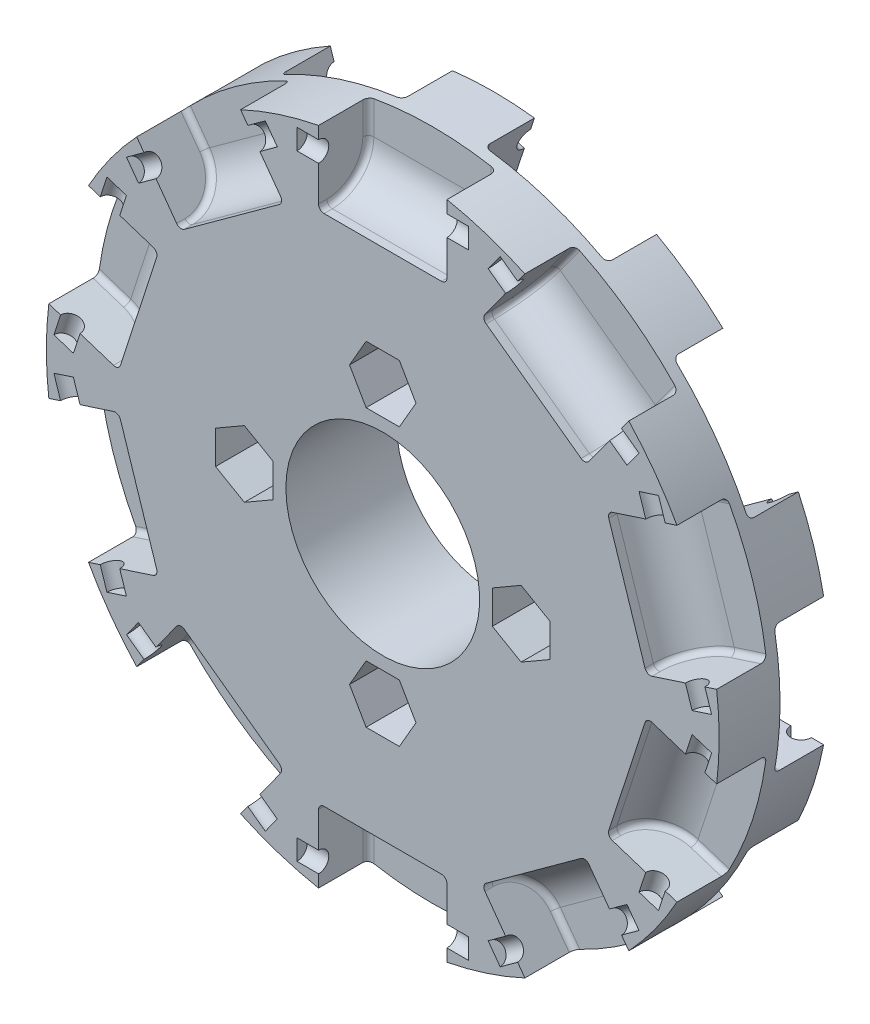
SolidWorks part; units mm, degrees
other "Markup1"
sketch "Sketch8" plane through (32.7336, 32.7336, 0) normal (0.5701, 0.1846, 0.8006) x (0.8043, 0.0736, -0.5897)
ref_plane "Front Plane" through (0, 0, 0) normal (0, 0, 1) x (1, 0, 0)
ref_plane "Top Plane" through (0, 0, 0) normal (0, 1, 0) x (1, 0, 0)
ref_plane "Right Plane" through (0, 0, 0) normal (1, 0, 0) x (0, 0, -1)
sketch "Sketch1" plane through (0, 0, 0) normal (0, 0, 1) x (1, 0, 0)
  circle A0 centre (0, 0) radius 38.5953
  dimension "D1" = 77.1906
extrude "Boss-Extrude2" add sketch "Sketch1" against normal blind 6.35
sketch "Sketch2" plane through (0, 0, 0) normal (0, 0, 1) x (1, 0, 0)
  line L1 (-12.7, 38.5953) -> (12.7, 38.5953) construction
  line L2 (-7.366, 39.8653) -> (7.366, 39.8653)
  line L3 (-7.366, 39.8653) -> (-7.366, 29.4513)
  line L4 (-7.366, 29.4513) -> (7.366, 29.4513)
  line L5 (7.366, 39.8653) -> (7.366, 29.4513)
  line L6 (-7.366, 39.8653) -> (7.366, 29.4513) construction
  line L7 (-7.366, 29.4513) -> (7.366, 39.8653) construction
  line L35 (0, 0) -> (0, 38.5953) construction
  circle A1 centre (0, 0) radius 38.5953 construction
  point P10 (0, 34.6583)
  circle M7 centre (0, 0) radius 38.5953
  dimension "D1" = 14.732
  dimension "D2" = 10.414
  dimension "D3" = 1.27
  dimension "D4" = 25.4
extrude "Cut-Extrude2" cut sketch "Sketch2" against normal blind 5.715 contours L5 L3 L4 M7
pattern_circular "CirPattern1" count 10 over 360 about axis through (0, 0, 0) along (0, 0, 1) of "Cut-Extrude2"
ref_plane "Plane1" through (0, 0, 0) normal (1, 0, 0) x (0, 0, -1)
sketch "Sketch4" plane through (0, 0, 0) normal (1, 0, 0) x (0, 0, -1)
  line L0 (5.715, 29.4513) -> (0, 29.4513) construction
  line L1 (0, 37.8859) -> (0, 29.4513) construction
  circle A0 centre (0, 35.2933) radius 1.1747
  dimension "D1" = 2.3495
  dimension "D2" = 5.842
extrude "Cut-Extrude4" cut sketch "Sketch4" against normal mid plane 19.685
pattern_circular "CirPattern2" count 10 over 360 about axis through (0, 0, 0) along (0, 0, 1) of "Cut-Extrude4"
sketch "Sketch6" plane through (0, 0, -6.35) normal (0, 0, -1) x (-1, 0, 0)
  line L0 (15.875, -3.8128) -> (19.177, -1.9064)
  line L1 (19.177, -1.9064) -> (19.177, 1.9064)
  line L2 (19.177, 1.9064) -> (15.875, 3.8128)
  line L3 (3.8128, 15.875) -> (1.9064, 19.177)
  line L4 (1.9064, 19.177) -> (-1.9064, 19.177)
  line L5 (-1.9064, 19.177) -> (-3.8128, 15.875)
  line L6 (-3.8128, 15.875) -> (-1.9064, 12.573)
  line L7 (-1.9064, 12.573) -> (1.9064, 12.573)
  line L8 (1.9064, 12.573) -> (3.8128, 15.875)
  line L9 (15.875, 3.8128) -> (12.573, 1.9064)
  line L10 (12.573, 1.9064) -> (12.573, -1.9064)
  line L11 (12.573, -1.9064) -> (15.875, -3.8128)
  line L12 (-3.8128, -15.875) -> (-1.9064, -19.177)
  line L13 (-1.9064, -19.177) -> (1.9064, -19.177)
  line L14 (1.9064, -19.177) -> (3.8128, -15.875)
  line L15 (3.8128, -15.875) -> (1.9064, -12.573)
  line L16 (1.9064, -12.573) -> (-1.9064, -12.573)
  line L17 (-1.9064, -12.573) -> (-3.8128, -15.875)
  line L18 (-15.875, 3.8128) -> (-19.177, 1.9064)
  line L19 (-19.177, 1.9064) -> (-19.177, -1.9064)
  line L20 (-19.177, -1.9064) -> (-15.875, -3.8128)
  line L21 (-15.875, -3.8128) -> (-12.573, -1.9064)
  line L22 (-12.573, -1.9064) -> (-12.573, 1.9064)
  line L23 (-12.573, 1.9064) -> (-15.875, 3.8128)
  circle A4 centre (0, 15.875) radius 3.302 construction
  circle A5 centre (15.875, 0) radius 3.302 construction
  circle A6 centre (0, -15.875) radius 3.302 construction
  circle A7 centre (-15.875, 0) radius 3.302 construction
  dimension "D3" = 4
  dimension "D1" = 6.604
  dimension "D2" = 15.875
extrude "Cut-Extrude7" cut sketch "Sketch6" against normal through all
sketch "Sketch9" plane through (0, 0, -6.35) normal (0, 0, -1) x (-1, 0, 0)
  line L7 (15.875, -3.8128) -> (19.177, -1.9064)
  line L8 (3.8128, 15.875) -> (1.9064, 19.177)
  line L9 (1.9064, 19.177) -> (-1.9064, 19.177)
  line L10 (-1.9064, 19.177) -> (-3.8128, 15.875)
  line L11 (-3.8128, 15.875) -> (-1.9064, 12.573)
  line L12 (-1.9064, 12.573) -> (1.9064, 12.573)
  line L13 (1.9064, 12.573) -> (3.8128, 15.875)
  line L14 (19.177, -1.9064) -> (19.177, 1.9064)
  line L15 (19.177, 1.9064) -> (15.875, 3.8128)
  line L16 (15.875, 3.8128) -> (12.573, 1.9064)
  line L17 (12.573, 1.9064) -> (12.573, -1.9064)
  line L18 (12.573, -1.9064) -> (15.875, -3.8128)
  line L19 (-3.8128, -15.875) -> (-1.9064, -19.177)
  line L20 (-1.9064, -19.177) -> (1.9064, -19.177)
  line L21 (1.9064, -19.177) -> (3.8128, -15.875)
  line L22 (3.8128, -15.875) -> (1.9064, -12.573)
  line L23 (1.9064, -12.573) -> (-1.9064, -12.573)
  line L24 (-1.9064, -12.573) -> (-3.8128, -15.875)
  line L25 (-15.875, 3.8128) -> (-19.177, 1.9064)
  line L26 (-19.177, 1.9064) -> (-19.177, -1.9064)
  line L27 (-19.177, -1.9064) -> (-15.875, -3.8128)
  line L28 (-15.875, -3.8128) -> (-12.573, -1.9064)
  line L29 (-12.573, -1.9064) -> (-12.573, 1.9064)
  line L30 (-12.573, 1.9064) -> (-15.875, 3.8128)
  circle A0 centre (0, 0) radius 38.5953
  circle A5 centre (0, 15.875) radius 3.302 construction
  circle A6 centre (15.875, 0) radius 3.302 construction
  circle A7 centre (0, -15.875) radius 3.302 construction
  circle A8 centre (-15.875, 0) radius 3.302 construction
  circle A9 centre (0, 0) radius 38.5953 construction
  dimension "D3" = 4
extrude "Boss-Extrude3" add sketch "Sketch9" along normal blind 6.35
sketch "Sketch10" plane through (0, 0, -12.7) normal (0, 0, -1) x (-1, 0, 0)
  line L0 (-24.6266, 36.7063) -> (0.7734, 36.7063) construction
  line L1 (-2.0955, 30.2861) -> (-16.1064, 25.7336)
  line L2 (-2.0955, 30.2861) -> (-5.3136, 40.1904)
  line L3 (-5.3136, 40.1904) -> (-19.3245, 35.6379)
  line L4 (-16.1064, 25.7336) -> (-19.3245, 35.6379)
  line L5 (-2.0955, 30.2861) -> (-19.3245, 35.6379) construction
  line L6 (-5.3136, 40.1904) -> (-16.1064, 25.7336) construction
  line L7 (0, 0) -> (-11.9266, 36.7063) construction
  line L8 (0, 0) -> (0, 40.3277) construction
  circle A2 centre (0, 0) radius 38.5953 construction
  point P8 (-10.71, 32.962)
  dimension "D1" = 1.27
  dimension "D2" = 14.732
  dimension "D3" = 10.414
  dimension "D4" = 25.4
  dimension "D5" = 18
extrude "Cut-Extrude8" cut sketch "Sketch10" against normal blind 5.715
pattern_circular "CirPattern3" count 10 over 360 about axis through (0, 0, 0) along (0, 0, 1) of "Cut-Extrude8"
ref_plane "Plane2" through (0, 0, 0) normal (-0.9511, 0.309, 0) x (0, 0, -1)
sketch "Sketch11" plane through (0, 0, 0) normal (-0.9511, 0.309, 0) x (0, 0, -1)
  line L5 (6.985, -29.4513) -> (12.7, -29.4513) construction
  line L6 (12.7, 18.7129) -> (12.7, 26.3207) construction
  circle A0 centre (12.7, -35.2933) radius 1.1748
  dimension "D1" = 2.3495
  dimension "D2" = 5.842
extrude "Cut-Extrude9" cut sketch "Sketch11" against normal mid plane 19.685
pattern_circular "CirPattern4" count 10 over 360 about axis through (0, 0, 0) along (0, 0, 1) of "Cut-Extrude9"
fillet "Fillet1" radius 4.7625 20 edges at (-28.0099, -9.101, -5.715) (-28.0099, 9.101, -5.715) (0, 29.4513, -5.715) (0, -29.4513, -5.715) (-17.311, -23.8266, -5.715) (-17.311, 23.8266, -5.715) (9.101, 28.0099, -6.985) (29.4513, 0, -6.985) (23.8266, -17.311, -6.985) (9.101, -28.0099, -6.985) (28.0099, -9.101, -5.715) (-9.101, -28.0099, -6.985) (-23.8266, -17.311, -6.985) (-29.4513, 0, -6.985) (-23.8266, 17.311, -6.985) (-9.101, 28.0099, -6.985) (23.8266, 17.311, -6.985) (17.311, -23.8266, -5.715) (17.311, 23.8266, -5.715) (28.0099, 9.101, -5.715)
fillet "Fillet2" radius 0.635 120 edges at (-32.0092, -18.1455, -5.715) (-36.5617, -4.1345, -5.715) (-36.5617, 4.1345, -5.715) (-32.0092, 18.1455, -5.715) (-7.366, 36.0498, -5.715) (7.366, -36.0498, -5.715) (-7.366, -36.0498, -5.715) (7.366, 36.0498, -5.715) (-15.2303, -33.4946, -5.715) (-27.1488, -24.8353, -5.715) (-27.1488, 24.8353, -5.715) (-15.2303, 33.4946, -5.715) (18.1455, 32.0092, -6.985) (36.0498, -7.366, -6.985) (24.8353, -27.1488, -6.985) (4.1345, -36.5617, -6.985) (-18.1455, -32.0092, -6.985) (36.5617, -4.1345, -5.715) (32.0092, -18.1455, -5.715) (-33.4946, -15.2303, -6.985) (-36.0498, 7.366, -6.985) (-24.8353, 27.1488, -6.985) (-4.1345, 36.5617, -6.985) (33.4946, 15.2303, -6.985) (27.1488, -24.8353, -5.715) (15.2303, -33.4946, -5.715) (15.2303, 33.4946, -5.715) (27.1488, 24.8353, -5.715) (-33.4946, 15.2303, -6.985) (-28.1562, 11.3518, -12.2238) (-29.2847, 12.1717, -8.3799) (-19.497, 23.2703, -12.2238) (-20.6255, 24.0902, -8.3799) (30.2861, 2.0955, -0.4762) (31.6127, 2.5265, -4.3201) (25.7336, 16.1064, -0.4762) (27.0603, 16.5375, -4.3201) (23.2703, 19.497, -0.4762) (24.0902, 20.6255, -4.3201) (11.3518, 28.1562, -0.4762) (12.1717, 29.2847, -4.3201) (-18.1455, 32.0092, -6.985) (-16.1064, 25.7336, -12.2238) (-16.5375, 27.0603, -8.3799) (-2.0955, 30.2861, -12.2238) (-2.5265, 31.6127, -8.3799) (25.7336, -16.1064, -0.4762) (27.0603, -16.5375, -4.3201) (30.2861, -2.0955, -0.4762) (31.6127, -2.5265, -4.3201) (-36.0498, -7.366, -6.985) (-29.4513, -7.366, -12.2238) (-30.8462, -7.366, -8.3799) (-29.4513, 7.366, -12.2238) (-30.8462, 7.366, -8.3799) (-24.8353, -27.1488, -6.985) (-19.497, -23.2703, -12.2238) (-20.6255, -24.0902, -8.3799) (-28.1562, -11.3518, -12.2238) (-29.2847, -12.1717, -8.3799) (11.3518, -28.1562, -0.4762) (12.1717, -29.2847, -4.3201) (23.2703, -19.497, -0.4762) (24.0902, -20.6255, -4.3201) (24.8353, 27.1488, -6.985) (19.497, 23.2703, -12.2238) (20.6255, 24.0902, -8.3799) (28.1562, 11.3518, -12.2238) (29.2847, 12.1717, -8.3799) (36.0498, 7.366, -6.985) (29.4513, 7.366, -12.2238) (30.8462, 7.366, -8.3799) (29.4513, -7.366, -12.2238) (30.8462, -7.366, -8.3799) (33.4946, -15.2303, -6.985) (28.1562, -11.3518, -12.2238) (29.2847, -12.1717, -8.3799) (19.497, -23.2703, -12.2238) (20.6255, -24.0902, -8.3799) (4.1345, 36.5617, -6.985) (2.0955, 30.2861, -12.2238) (2.5265, 31.6127, -8.3799) (16.1064, 25.7336, -12.2238) (16.5375, 27.0603, -8.3799) (-4.1345, -36.5617, -6.985) (-2.0955, -30.2861, -12.2238) (-2.5265, -31.6127, -8.3799) (-16.1064, -25.7336, -12.2238) (-16.5375, -27.0603, -8.3799) (18.1455, -32.0092, -6.985) (16.1064, -25.7336, -12.2238) (16.5375, -27.0603, -8.3799) (2.0955, -30.2861, -12.2238) (2.5265, -31.6127, -8.3799) (-25.7336, 16.1064, -0.4762) (-27.0603, 16.5375, -4.3201) (-30.2861, 2.0955, -0.4762) (-31.6127, 2.5265, -4.3201) (-30.2861, -2.0955, -0.4762) (-31.6127, -2.5265, -4.3201) (-25.7336, -16.1064, -0.4762) (-27.0603, -16.5375, -4.3201) (-23.2703, -19.497, -0.4762) (-24.0902, -20.6255, -4.3201) (-11.3518, -28.1562, -0.4762) (-12.1717, -29.2847, -4.3201) (-7.366, -29.4513, -0.4762) (-7.366, -30.8462, -4.3201) (7.366, -29.4513, -0.4762) (7.366, -30.8462, -4.3201) (7.366, 29.4513, -0.4762) (7.366, 30.8462, -4.3201) (-7.366, 29.4513, -0.4762) (-7.366, 30.8462, -4.3201) (-11.3518, 28.1562, -0.4762) (-12.1717, 29.2847, -4.3201) (-23.2703, 19.497, -0.4762) (-24.0902, 20.6255, -4.3201) (32.0092, 18.1455, -5.715) (36.5617, 4.1345, -5.715)
sketch "Sketch12" plane through (0, 0, -12.7) normal (0, 0, -1) x (-1, 0, 0)
  circle A0 centre (0, 0) radius 11.1125
  dimension "D1" = 22.225
extrude "Cut-Extrude10" cut sketch "Sketch12" against normal through all
